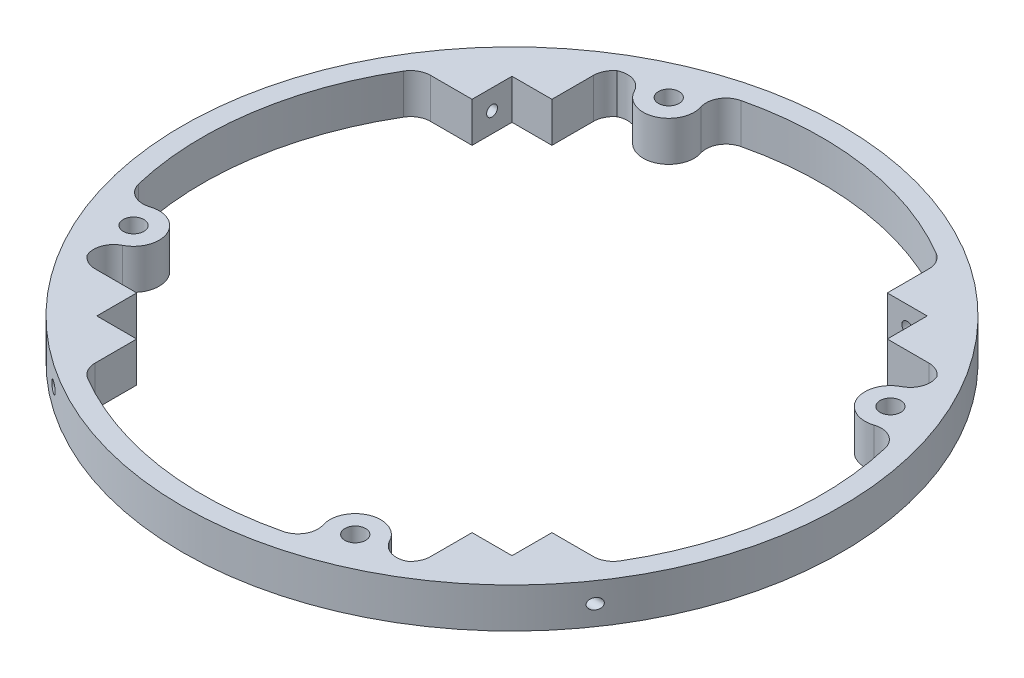
SolidWorks part; units mm, degrees
material "6061-T6 (SS)"
ref_plane "Front Plane" through (0, 0, 0) normal (0, 0, 1) x (1, 0, 0)
ref_plane "Top Plane" through (0, 0, 0) normal (0, 1, 0) x (1, 0, 0)
ref_plane "Right Plane" through (0, 0, 0) normal (1, 0, 0) x (0, 0, -1)
sketch "Sketch1" plane through (0, 0, 0) normal (0, 1, 0) x (1, 0, 0)
  line L0 (0, 0) -> (0, 84.2831) construction
  line L1 (-52, 52) -> (52, 52) construction
  line L2 (-52, 52) -> (-52, -52) construction
  line L3 (-52, -52) -> (52, -52) construction
  line L4 (52, 52) -> (52, -52) construction
  line L5 (0, 0) -> (-99.9306, 0) construction
  line L6 (0, 0) -> (-52, 52) construction
  line L7 (0, 0) -> (-31.8699, 76.9407) construction
  line L8 (-42, 52) -> (-52, 52)
  line L9 (-52, 52) -> (-52, 42)
  line L10 (-52, 42) -> (-65.192, 42)
  line L11 (-42, 52) -> (-42, 65.192)
  line L12 (-35.4887, 68.9533) -> (-33.6765, 64.5783)
  line L13 (-23.663, 73.8516) -> (-21.8509, 69.4766)
  line L14 (42, 52) -> (42, 65.192)
  line L15 (52, 52) -> (42, 52)
  line L16 (52, 42) -> (52, 52)
  line L17 (52, 42) -> (65.192, 42)
  line L18 (68.9533, 35.4887) -> (64.5783, 33.6765)
  line L19 (73.8516, 23.663) -> (69.4766, 21.8509)
  line L20 (52, -42) -> (65.192, -42)
  line L21 (52, -52) -> (52, -42)
  line L22 (42, -52) -> (52, -52)
  line L23 (42, -52) -> (42, -65.192)
  line L24 (35.4887, -68.9533) -> (33.6765, -64.5783)
  line L25 (23.663, -73.8516) -> (21.8509, -69.4766)
  line L26 (-42, -52) -> (-42, -65.192)
  line L27 (-52, -52) -> (-42, -52)
  line L28 (-52, -42) -> (-52, -52)
  line L29 (-52, -42) -> (-65.192, -42)
  line L30 (-68.9533, -35.4887) -> (-64.5783, -33.6765)
  line L31 (-73.8516, -23.663) -> (-69.4766, -21.8509)
  circle A0 centre (0, 0) radius 82.55
  arc A1 (-65.192, 42) -> (-77.55, 0) centre (0, 0) ccw
  arc A2 (-42, 65.192) -> (-35.4887, 68.9533) centre (0, 0) cw
  arc A3 (-33.6765, 64.5783) -> (-21.8509, 69.4766) centre (-27.7637, 67.0275) ccw
  arc A4 (0, 77.55) -> (-23.663, 73.8516) centre (0, 0) ccw
  arc A5 (42, 65.192) -> (0, 77.55) centre (0, 0) ccw
  arc A6 (65.192, 42) -> (68.9533, 35.4887) centre (0, 0) cw
  arc A7 (64.5783, 33.6765) -> (69.4766, 21.8509) centre (67.0275, 27.7637) ccw
  arc A8 (77.55, 0) -> (73.8516, 23.663) centre (0, 0) ccw
  arc A9 (65.192, -42) -> (77.55, 0) centre (0, 0) ccw
  arc A10 (42, -65.192) -> (35.4887, -68.9533) centre (0, 0) cw
  arc A11 (33.6765, -64.5783) -> (21.8509, -69.4766) centre (27.7637, -67.0275) ccw
  arc A12 (0, -77.55) -> (23.663, -73.8516) centre (0, 0) ccw
  arc A13 (-42, -65.192) -> (0, -77.55) centre (0, 0) ccw
  arc A14 (-65.192, -42) -> (-68.9533, -35.4887) centre (0, 0) cw
  arc A15 (-64.5783, -33.6765) -> (-69.4766, -21.8509) centre (-67.0275, -27.7637) ccw
  arc A16 (-77.55, 0) -> (-73.8516, -23.663) centre (0, 0) ccw
  point P21 (-22.7569, 71.6641)
  point P61 (0, 0)
  dimension "D1" = 165.1
  dimension "D2" = 104
  dimension "D3" = 22.5
  dimension "D4" = 5
  dimension "D5" = 72.55
  dimension "D6" = 12.8
  dimension "D7" = 10
  dimension "D8" = 4
extrude "Boss-Extrude1" add sketch "Sketch1" along normal blind 10
fillet "Fillet1" radius 5 16 edges at (-73.8516, 5, 23.663) (-68.9533, 5, 35.4887) (-42, 5, 65.192) (-65.192, 5, 42) (23.663, 5, 73.8516) (35.4887, 5, 68.9533) (42, 5, 65.192) (65.192, 5, 42) (73.8516, 5, -23.663) (68.9533, 5, -35.4887) (65.192, 5, -42) (42, 5, -65.192) (-35.4887, 5, -68.9533) (-23.663, 5, -73.8516) (-42, 5, -65.192) (-65.192, 5, -42)
hole_wizard "#6 (0.204) Diameter Hole1" positions "Sketch4" profile "Sketch3" hole size "#6" standard "ANSI Inch" end condition through all
sketch "Sketch4" plane through (0, 10, 0) normal (0, 1, 0) x (1, 0, 0)
  point P0 (67.0275, 27.7637)
sketch "Sketch3" plane through (67.0275, 10, -27.7637) normal (1, 0, 0) x (0, 0, 1)
  line L0 (0, 0) -> (0, 10)
  line L1 (0, 10) -> (2.5908, 10)
  line L2 (2.5908, 10) -> (2.5908, 0)
  line L5 (2.5908, 0) -> (0, 0)
  line L11 (0, -6.35) -> (0, 107.95) construction
  dimension "Thru Hole Dia." = 5.1816
  dimension "Thru Hole Depth" = 10
hole_wizard "#6-32 Tapped Hole2" positions "Sketch8" profile "Sketch9" tap size "#6-32" standard "ANSI Inch" end condition through all
sketch "Sketch8" plane through (0, 0, -52) normal (0, 0, 1) x (1, 0, 0)
  line L0 (52, 0) -> (42, 10)
  point P0 (47, 5)
  point P10 (47, 5)
sketch "Sketch9" plane through (47, 5, -52) normal (1, 0, 0) x (0, -1, 0)
  line L0 (0, 0) -> (0, 30.55)
  line L1 (0, 30.55) -> (1.3525, 30.55)
  line L2 (1.3525, 30.55) -> (1.3525, 0)
  line L5 (1.3525, 0) -> (0, 0)
  line L11 (0, -6.35) -> (0, 107.95) construction
  dimension "Thru Tap Drill Dia." = 2.7051
  dimension "Thru Tap Drill Depth" = 30.55
cosmetic thread "Hole Thread2" parameters "D2"=3.5052
ref_axis "Axis1" through (0, 10.5, 0) along (0, -1, 0)
pattern_circular "CirPattern1" count 4 over 360 about axis through (0, 10.5, 0) along (0, -1, 0) of "#6 (0.204) Diameter Hole1", "#6-32 Tapped Hole2"
equation "\"TubeDiameter\"= 6.500in"
equation "\"D1@Sketch1\"=\"TubeDiameter\""
equation "\"D5@Sketch1\"=\"TubeDiameter\"/2-10mm"
